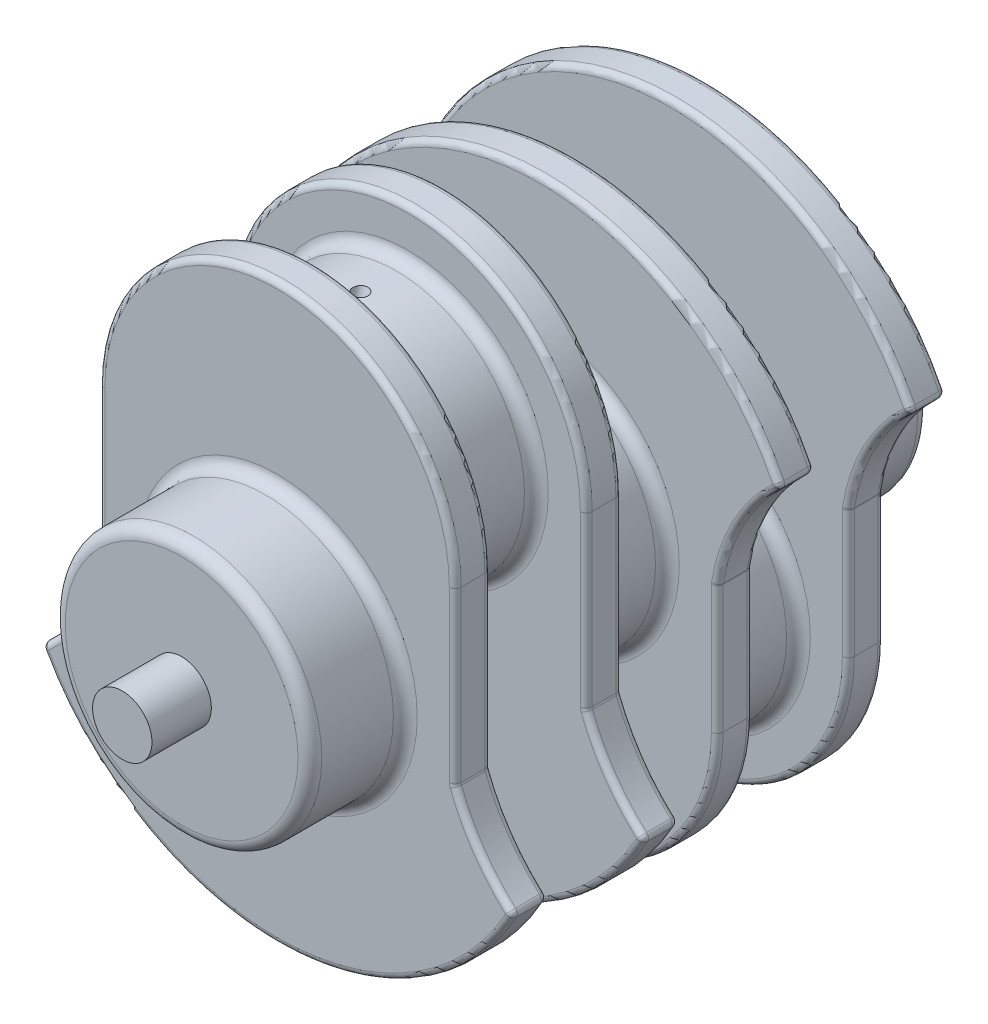
SolidWorks part; units mm, degrees
material "AISI 4340 Steel, normalized"
ref_plane "Front Plane" through (0, 0, 0) normal (0, 0, 1) x (1, 0, 0)
ref_plane "Top Plane" through (0, 0, 0) normal (0, 1, 0) x (1, 0, 0)
ref_plane "Right Plane" through (0, 0, 0) normal (1, 0, 0) x (0, 0, -1)
sketch "Sketch1" plane through (0, 0, 0) normal (0, 0, 1) x (1, 0, 0)
  circle A0 centre (0, 0) radius 43.2
  dimension "D1" = 43.2
extrude "Boss-Extrude1" add sketch "Sketch1" along normal blind 32.13
sketch "Sketch8" plane through (0, 0, 0) normal (0, 0, -1) x (-1, 0, 0)
  line L0 (-60, 43.2) -> (-60, -14.1284)
  line L1 (60, 43.2) -> (60, -14.1284)
  arc A0 (60, 43.2) -> (-60, 43.2) centre (0, 43.2) ccw
  arc A5 (-79.4533, -42.275) -> (79.4533, -42.275) centre (0, 0) ccw
  arc A6 (-60, -14.1284) -> (-79.4533, -42.275) centre (-125, 10) cw
  arc A7 (60, -14.1284) -> (79.4533, -42.275) centre (125, 10) ccw
  dimension "D1" = 60
  dimension "D2" = 90
  dimension "D3" = 43.2
  dimension "D5" = 10
  dimension "D6" = 125
extrude "Boss-Extrude5" add sketch "Sketch8" along normal blind 12
sketch "Sketch2" plane through (0, 0, 32.13) normal (0, 0, 1) x (1, 0, 0)
  circle A0 centre (0, 0) radius 10
  dimension "D1" = 10
extrude "Boss-Extrude2" add sketch "Sketch2" along normal blind 20
sketch "Sketch9" plane through (0, 0, -12) normal (0, 0, -1) x (-1, 0, 0)
  circle A0 centre (0, 43.2) radius 43.2
  dimension "D2" = 43.2
  dimension "D1" = 43.2
extrude "Boss-Extrude6" add sketch "Sketch9" along normal blind 32.13
ref_plane "Plane4" through (0, 0, -88.26) normal (0, 0, -1) x (-1, 0, 0)
sketch "Sketch10" plane through (0, 0, -44.13) normal (0, 0, -1) x (-1, 0, 0)
  line L0 (-60, -43.2) -> (-60, 0)
  line L1 (60, -43.2) -> (60, 0)
  arc A0 (-60, -43.2) -> (60, -43.2) centre (0, -43.2) ccw
  arc A1 (-60, 0) -> (-81.1187, 38.984) centre (-125, -10) ccw
  arc A2 (60, 0) -> (81.1187, 38.984) centre (125, -10) cw
  arc A3 (-81.1187, 38.984) -> (81.1187, 38.984) centre (0, 0) cw
  dimension "D2" = 43.2
  dimension "D1" = 60
  dimension "D5" = 10
  dimension "D3" = 90
  dimension "D4" = 125
extrude "Boss-Extrude7" add sketch "Sketch10" along normal blind 12 from surface starting at plane "Plane4"
ref_plane "Plane3" through (0, 0, -132.39) normal (0, 0, -1) x (-1, 0, 0)
sketch "Sketch12" plane through (0, 0, -132.39) normal (0, 0, -1) x (-1, 0, 0)
  line L2 (60, -43.2) -> (60, 0)
  line L3 (60, -43.2) -> (60, 0)
  line L4 (-60, 0) -> (-60, -43.2)
  line L5 (-60, 0) -> (-60, -43.2)
  arc A12 (-60, -43.2) -> (60, -43.2) centre (0, -43.2) ccw
  arc A13 (81.1187, 38.984) -> (60, 0) centre (125, -10) ccw
  arc A14 (81.1187, 38.984) -> (-81.1187, 38.984) centre (0, 0) ccw
  arc A15 (-60, 0) -> (-81.1187, 38.984) centre (-125, -10) ccw
  arc A16 (-60, -43.2) -> (60, -43.2) centre (0, -43.2) ccw
  arc A17 (81.1187, 38.984) -> (60, 0) centre (125, -10) ccw
  arc A18 (81.1187, 38.984) -> (-81.1187, 38.984) centre (0, 0) ccw
  arc A19 (-60, 0) -> (-81.1187, 38.984) centre (-125, -10) ccw
  dimension "D1" = 0
extrude "Boss-Extrude8" add sketch "Sketch12" along normal blind 12
sketch "Sketch14" plane through (0, 0, -100.26) normal (0, 0, -1) x (-1, 0, 0)
  circle A0 centre (0, -43.2) radius 43.2
  dimension "D2" = 43.2
  dimension "D1" = 43.2
extrude "Boss-Extrude9" add sketch "Sketch14" along normal up to next
sketch "Sketch15" plane through (0, 0, -144.39) normal (0, 0, -1) x (-1, 0, 0)
  circle A1 centre (0, 0) radius 43.2
  circle A2 centre (0, 0) radius 43.2
  dimension "D1" = 0
extrude "Boss-Extrude10" add sketch "Sketch15" along normal blind 32.13
sketch "Sketch16" plane through (0, 0, -176.52) normal (0, 0, -1) x (-1, 0, 0)
  circle A1 centre (0, 0) radius 10
  circle A2 centre (0, 0) radius 10
  dimension "D1" = 0
extrude "Boss-Extrude11" add sketch "Sketch16" along normal blind 20
sketch "Sketch18" plane through (0, 0, -44.13) normal (0, 0, -1) x (-1, 0, 0)
  line L2 (-60, 43.2) -> (-60, -14.1284)
  line L3 (-60, 43.2) -> (-60, -14.1284)
  line L4 (60, -14.1284) -> (60, 43.2)
  line L5 (60, -14.1284) -> (60, 43.2)
  arc A4 (60, 43.2) -> (-60, 43.2) centre (0, 43.2) ccw
  arc A5 (-79.4533, -42.275) -> (-60, -14.1284) centre (-125, 10) ccw
  arc A6 (-79.4533, -42.275) -> (79.4533, -42.275) centre (0, 0) ccw
  arc A7 (60, -14.1284) -> (79.4533, -42.275) centre (125, 10) ccw
  arc A8 (60, 43.2) -> (-60, 43.2) centre (0, 43.2) ccw
  arc A9 (-79.4533, -42.275) -> (-60, -14.1284) centre (-125, 10) ccw
  arc A10 (-79.4533, -42.275) -> (79.4533, -42.275) centre (0, 0) ccw
  arc A11 (60, -14.1284) -> (79.4533, -42.275) centre (125, 10) ccw
  dimension "D1" = 0
extrude "Boss-Extrude12" add sketch "Sketch18" along normal blind 12
sketch "Sketch19" plane through (0, 0, -56.13) normal (0, 0, -1) x (-1, 0, 0)
  circle A1 centre (0, 0) radius 43.2
  circle A2 centre (0, 0) radius 43.2
  dimension "D1" = 0
extrude "Boss-Extrude13" add sketch "Sketch19" along normal up to next
fillet "Fillet1" radius 2 32 edges at (0, -90, -44.13) (-67.9632, -29.4205, -44.13) (-60, 14.5358, -44.13) (60, 14.5358, -44.13) (67.9632, -29.4205, -44.13) (0, -90, -56.13) (-67.9632, -29.4205, -56.13) (-60, 14.5358, -56.13) (0, 103.2, -56.13) (60, 14.5358, -56.13) (67.9632, -29.4205, -56.13) (79.4533, -42.275, -50.13) (60, -14.1284, -50.13) (-60, -14.1284, -50.13) (-79.4533, -42.275, -50.13) (0, 103.2, -44.13) (60, 14.5358, 0) (67.9632, -29.4205, 0) (0, -90, 0) (-67.9632, -29.4205, 0) (-60, 14.5358, 0) (0, 103.2, -12) (60, 14.5358, -12) (67.9632, -29.4205, -12) (0, -90, -12) (-67.9632, -29.4205, -12) (-60, 14.5358, -12) (-60, -14.1284, -6) (-79.4533, -42.275, -6) (79.4533, -42.275, -6) (60, -14.1284, -6) (0, 103.2, 0)
fillet "Fillet2" radius 2 16 edges at (0, 90, -132.39) (67.1751, 21.3254, -132.39) (60, -21.6, -132.39) (0, -103.2, -132.39) (-60, -21.6, -132.39) (-67.1751, 21.3254, -132.39) (67.1751, 21.3254, -144.39) (60, -21.6, -144.39) (0, -103.2, -144.39) (-60, -21.6, -144.39) (-67.1751, 21.3254, -144.39) (-81.1187, 38.984, -138.39) (-60, 0, -138.39) (60, 0, -138.39) (81.1187, 38.984, -138.39) (0, 90, -144.39)
fillet "Fillet3" radius 2 16 edges at (60, -21.6, -88.26) (67.1751, 21.3254, -88.26) (0, 90, -88.26) (-67.1751, 21.3254, -88.26) (-60, -21.6, -88.26) (0, -103.2, -88.26) (60, -21.6, -100.26) (67.1751, 21.3254, -100.26) (-67.1751, 21.3254, -100.26) (-60, -21.6, -100.26) (0, -103.2, -100.26) (60, 0, -94.26) (81.1187, 38.984, -94.26) (-81.1187, 38.984, -94.26) (-60, 0, -94.26) (0, 90, -100.26)
fillet "Fillet5" radius 4 2 edges at (43.2, 0, 32.13) (43.2, 0, 0)
fillet "Fillet6" radius 4 2 edges at (-43.2, 0, -144.39) (-43.2, 0, -176.52)
ref_plane "Plane5" through (0, 31.75, 0) normal (0, 1, 0) x (1, 0, 0)
sketch "Sketch20" plane through (0, 0, 0) normal (1, 0, 0) x (0, 0, -1)
  line L1 (100.26, -86.4) -> (100.26, 0)
  line L2 (100.26, -86.4) -> (100.26, 0)
  dimension "D1" = 0
ref_plane "Plane6" through (0, -86.4, 0) normal (0, 1, 0) x (1, 0, 0)
sketch "Sketch21" plane through (0, 31.75, 0) normal (0, 1, 0) x (1, 0, 0)
  line L2 (-43.2, 172.52) -> (43.2, 172.52) construction
  line L3 (-43.2, 172.52) -> (-43.2, 148.39) construction
  line L4 (-43.2, 148.39) -> (43.2, 148.39) construction
  line L5 (43.2, 172.52) -> (43.2, 148.39) construction
  circle A0 centre (0, 160.455) radius 2.5
  point P10 (0, 172.52)
  point P11 (43.2, 160.455)
  dimension "D1" = 5
sketch "Sketch27" plane through (0, 0, 0) normal (0, 0, 1) x (1, 0, 0)
  line L0 (0, 86.4) -> (0, -43.2) construction
  circle A1 centre (0, 43.2) radius 43.2
  circle A2 centre (0, 43.2) radius 43.2 construction
  circle A3 centre (0, 0) radius 43.2
  circle A4 centre (0, 0) radius 43.2 construction
  dimension "D1" = 0
  dimension "D2" = 0
ref_plane "Plane8" through (0, 86.4, 0) normal (0, -1, 0) x (-1, 0, 0)
ref_plane "Plane9" through (0, -43.2, 0) normal (0, -1, 0) x (-1, 0, 0)
sketch "Sketch28" plane through (0, -43.2, 0) normal (0, -1, 0) x (-1, 0, 0)
  line L1 (-43.2, -4) -> (43.2, -4) construction
  line L2 (-43.2, -4) -> (-43.2, -28.13) construction
  line L3 (-43.2, -28.13) -> (43.2, -28.13) construction
  line L4 (43.2, -4) -> (43.2, -28.13) construction
  line L5 (-43.2, -4) -> (43.2, -28.13) construction
  line L6 (-43.2, -28.13) -> (43.2, -4) construction
  circle A0 centre (0, -16.065) radius 2.5
  point P4 (0, -16.065)
  dimension "D1" = 5
sketch "Sketch29" plane through (0, 86.4, 0) normal (0, -1, 0) x (-1, 0, 0)
  line L1 (43.2, 44.13) -> (-43.2, 44.13) construction
  line L2 (43.2, 44.13) -> (43.2, 12) construction
  line L3 (43.2, 12) -> (-43.2, 12) construction
  line L4 (-43.2, 44.13) -> (-43.2, 12) construction
  line L5 (43.2, 44.13) -> (-43.2, 12) construction
  line L6 (43.2, 12) -> (-43.2, 44.13) construction
  circle A0 centre (0, 28.065) radius 2.5
  point P4 (0, 28.065)
  dimension "D1" = 5
sketch "Sketch31" plane through (0, 0, 0) normal (1, 0, 0) x (0, 0, -1)
  line L0 (28.065, 86.4) -> (-16.065, -43.2) construction
ref_plane "Plane10" through (0, 86.4, -28.065) normal (0, -0.9466, 0.3223) x (-1, 0, 0)
ref_plane "Plane11" through (0, -43.2, 16.065) normal (0, -0.9466, 0.3223) x (-1, 0, 0)
combine bodies "Combine1" operation type add bodies to combine 119 109 117
fillet "Fillet7" radius 4 6 edges at (-43.2, 43.2, -44.13) (-43.2, 43.2, -12) (-43.2, 0, -56.13) (-43.2, 0, -88.26) (-43.2, -43.2, -132.39) (-43.2, -43.2, -100.26)
sketch "Sketch39" plane through (0, -86.4, 0) normal (0, 1, 0) x (1, 0, 0)
  line L1 (43.2, 128.39) -> (-43.2, 128.39) construction
  line L2 (43.2, 128.39) -> (43.2, 104.26) construction
  line L3 (43.2, 104.26) -> (-43.2, 104.26) construction
  line L4 (-43.2, 128.39) -> (-43.2, 104.26) construction
  line L5 (43.2, 128.39) -> (-43.2, 104.26) construction
  line L6 (43.2, 104.26) -> (-43.2, 128.39) construction
  point P4 (0, 116.325)
sketch "Sketch40" plane through (0, 0, 0) normal (1, 0, 0) x (0, 0, -1)
  line L0 (160.455, 31.75) -> (116.325, -86.4) construction
  line L1 (172.52, 31.75) -> (148.39, 31.75) construction
ref_plane "Plane12" through (0, 31.75, -160.455) normal (0, -0.9368, 0.3499) x (-1, 0, 0)
ref_plane "Plane13" through (0, -86.4, -116.325) normal (0, -0.9368, 0.3499) x (-1, 0, 0)
sketch "Sketch47" plane through (0, 86.4, -28.065) normal (0, -0.9466, 0.3223) x (-1, 0, 0)
  ellipse E0 centre (0, 0) end of major axis (2.5, 0) minor radius 2.3666 construction
  ellipse E1 centre (0, 0) end of major axis (2.5, 0) minor radius 2.3666
extrude "Cut-Extrude1" cut sketch "Sketch47" along normal through all
sketch "Sketch48" plane through (0, -43.2, 16.065) normal (0, -0.9466, 0.3223) x (-1, 0, 0)
  ellipse E0 centre (0, 0) end of major axis (2.5, 0) minor radius 2.3666 construction
  ellipse E1 centre (0, 0) end of major axis (2.5, 0) minor radius 2.3666
extrude "Cut-Extrude2" cut sketch "Sketch48" against normal through all
sketch "Sketch49" plane through (0, -86.4, -116.325) normal (0, -0.9368, 0.3499) x (-1, 0, 0)
  circle A0 centre (0, 0) radius 2.5
  dimension "D1" = 5
extrude "Cut-Extrude3" cut sketch "Sketch49" against normal through all
sketch "Sketch50" plane through (0, 31.75, -160.455) normal (0, -0.9368, 0.3499) x (-1, 0, 0)
  circle A0 centre (0, 0) radius 2.5 construction
  circle A1 centre (0, 0) radius 2.5
extrude "Cut-Extrude4" cut sketch "Sketch50" along normal through all
equation "\"CRR\"= 43.2mm'Crank Radius"
equation "\"D1@Sketch9\"=\"CRR\""
equation "\"D1@Sketch14\"=\"CRR\""
equation "\"JR\"= 43.2mm'Journal Radius"
equation "\"D1@Sketch1\"=\"JR\""
equation "\"D2@Sketch9\"=\"JR\""
equation "\"D2@Sketch14\"=\"JR\""
equation "\"LT\"= 12mm'Lobe Thickness"
equation "\"D1@Boss-Extrude5\"=\"LT\""
equation "\"D1@Boss-Extrude7\"=\"LT\""
equation "\"D1@Boss-Extrude8\"=\"LT\""
equation "\"D1@Boss-Extrude12\"=\"LT\""
equation "\"D3@Sketch8\"=\"CRR\""
equation "\"D2@Sketch10\"=\"CRR\""
equation "\"JL\"= 24.13 + 2 * ( \"JF\" )'Journal Length"
equation "\"D1@Boss-Extrude1\"=\"JL\""
equation "\"D1@Boss-Extrude6\"=\"JL\""
equation "\"D1@Boss-Extrude10\"=\"JL\""
equation "\"LHD\"= 5mm'Lubrication Hole Diameter"
equation "\"D1@Sketch29\"=\"LHD\""
equation "\"JF\"= 4mm'Internal Journal Fillets"
equation "\"D1@Fillet7\"=\"JF\""
equation "\"D1@Fillet6\"=\"JF\""
equation "\"LR\" = 60mm'Lobe radius"
equation "\"CWR\" = 90mm'Counterweight Radius"
equation "\"D1@Sketch8\"=\"LR\""
equation "\"D2@Sketch8\"=\"CWR\""
equation "\"D3@Sketch10\"=\"CWR\""
equation "\"D1@Sketch10\"=\"LR\""
